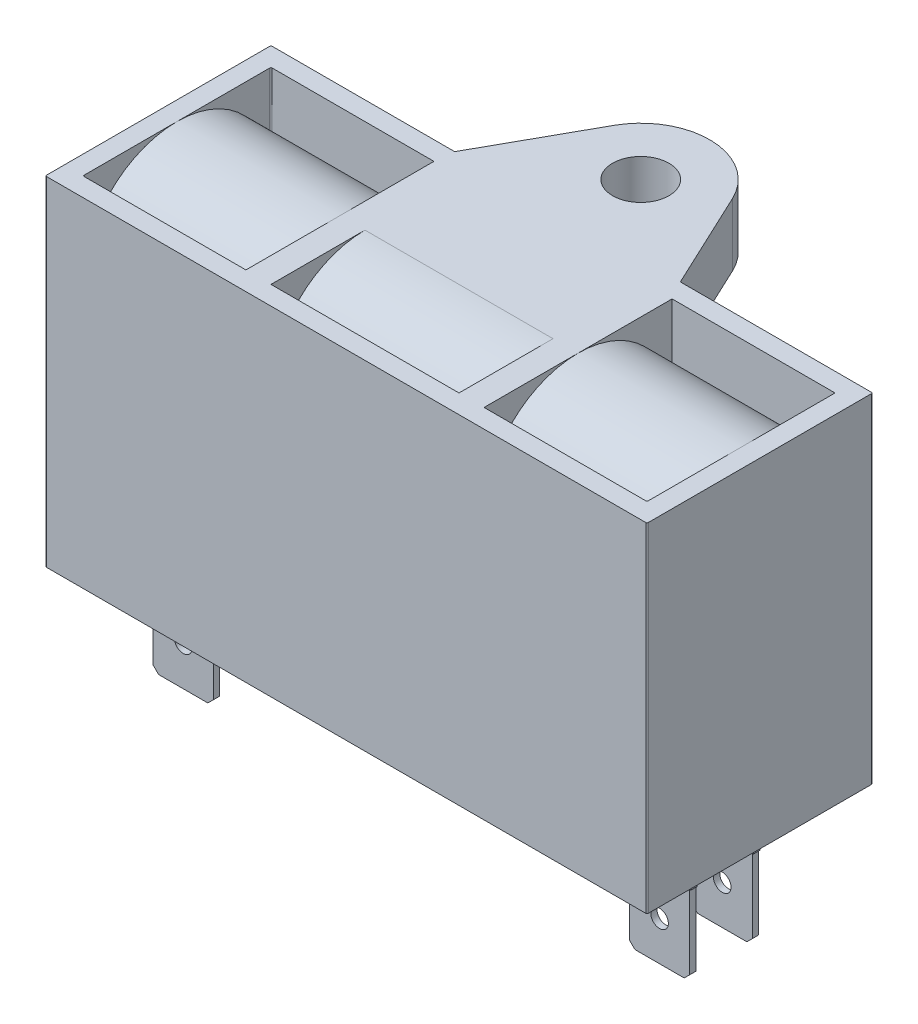
SolidWorks part; units mm, degrees
ref_plane "Front Plane" through (0, 0, 0) normal (0, 0, 1) x (1, 0, 0)
ref_plane "Top Plane" through (0, 0, 0) normal (0, 1, 0) x (1, 0, 0)
ref_plane "Right Plane" through (0, 0, 0) normal (1, 0, 0) x (0, 0, -1)
sketch "Sketch1" plane through (0, 0, 0) normal (0, 1, 0) x (1, 0, 0)
  line L1 (-24, 9) -> (24, 9)
  line L2 (-24, 9) -> (-24, -9)
  line L3 (-24, -9) -> (24, -9)
  line L4 (24, 9) -> (24, -9)
  line L5 (-24, 9) -> (24, -9) construction
  line L6 (-24, -9) -> (24, 9) construction
  point P0 (0, 0)
  dimension "D1" = 48
  dimension "D2" = 18
extrude "Boss-Extrude1" add sketch "Sketch1" along normal blind 27
sketch "Sketch7" plane through (0, 27, 0) normal (0, 1, 0) x (1, 0, 0)
  line L14 (22.5, -7.5) -> (22.5, 7.5)
  line L15 (22.5, 7.5) -> (-22.5, 7.5)
  line L16 (-22.5, 7.5) -> (-22.5, -7.5)
  line L17 (-22.5, -7.5) -> (22.5, -7.5)
  line L18 (22.5, -7.5) -> (22.5, 7.5)
  line L19 (22.5, 7.5) -> (-22.5, 7.5)
  line L20 (-22.5, 7.5) -> (-22.5, -7.5)
  line L21 (-22.5, -7.5) -> (22.5, -7.5)
  dimension "D1" = 1.5
extrude "Cut-Extrude8" cut sketch "Sketch7" against normal through all
sketch "Sketch9" plane through (22.5, 0, 0) normal (-1, 0, 0) x (0, 0, 1)
  line L0 (7.5, 27) -> (-7.5, 27) construction
  line L1 (-7.5, 0) -> (-7.5, 27) construction
  line L2 (7.5, 0) -> (7.5, 27) construction
  line L3 (-7.5, 0) -> (-7.5, 19.5)
  line L4 (7.5, 0) -> (7.5, 19.5)
  line L5 (7.5, 0) -> (-7.5, 0) construction
  line L6 (7.5, 0) -> (-7.5, 0)
  arc A0 (7.5, 19.5) -> (-7.5, 19.5) centre (0, 19.5) ccw
extrude "Boss-Extrude4" add sketch "Sketch9" along normal up to next separate body
sketch "Sketch10" plane through (0, 27, 0) normal (0, 1, 0) x (1, 0, 0)
  line L0 (24, 9) -> (-24, 9) construction
  line L1 (-7.5, 9) -> (-9.5, 9)
  line L2 (-7.5, 9) -> (-7.5, -9)
  line L3 (-7.5, -9) -> (-9.5, -9)
  line L4 (-9.5, 9) -> (-9.5, -9)
  line L5 (-24, -9) -> (24, -9) construction
  line L7 (-22.5, 7.5) -> (-22.5, -7.5) construction
  line L8 (22.5, -7.5) -> (22.5, 7.5) construction
  line L9 (7.5, 9) -> (9.5, 9)
  line L10 (7.5, 9) -> (7.5, -9)
  line L11 (7.5, -9) -> (9.5, -9)
  line L12 (9.5, 9) -> (9.5, -9)
  line M7 (22.5, -7.5) -> (-22.5, -7.5)
  line M9 (-22.5, 7.5) -> (22.5, 7.5)
  dimension "D1" = 13
  dimension "D2" = 2
  dimension "D3" = 2
  dimension "D4" = 13
extrude "Boss-Extrude5" add sketch "Sketch10" against normal up to next (27 mm away) contours L12 L10 M9 M7 | L4 L2 M9 M7 region at (-8.5, 27, 0) region at (8.5, 27, 0)
sketch "Sketch11" plane through (0, 27, 0) normal (0, 1, 0) x (1, 0, 0)
  line L0 (0, 9) -> (0, 14.5) construction
  line L1 (24, 9) -> (-24, 9) construction
  line L5 (-9.3433, 9) -> (8.6567, 9)
  line L10 (-9.3433, 9) -> (-4.8089, 17.1692)
  line L11 (8.6567, 9) -> (4.979, 16.8366)
  circle A0 centre (0, 14.5) radius 2.25
  arc A2 (4.979, 16.8366) -> (-4.8089, 17.1692) centre (0, 14.5) ccw
  point P9 (0, 9)
  line M22 (24, 9) -> (-24, 9)
  dimension "D2" = 4.5
  dimension "D1" = 5.5
  dimension "D3" = 18
extrude "Boss-Extrude7" add sketch "Sketch11" against normal blind 5 contours A0 M22 region at (-6.8916, 27, -12.9822)
fillet "Fillet1" radius 0.5 1 edges at (-0.3433, 22, -9)
sketch "Sketch12" plane through (0, 0, 0) normal (0, -1, 0) x (1, 0, 0)
  line L8 (22.5, -7.5) -> (22.5, 7.5)
  line L9 (22.5, 7.5) -> (-22.5, 7.5)
  line L10 (-22.5, 7.5) -> (-22.5, -7.5)
  line L11 (-22.5, -7.5) -> (22.5, -7.5)
  line L12 (22.5, -7.5) -> (22.5, 7.5)
  line L13 (22.5, 7.5) -> (-22.5, 7.5)
  line L14 (-22.5, 7.5) -> (-22.5, -7.5)
  line L15 (-22.5, -7.5) -> (22.5, -7.5)
  dimension "D1" = 1.5
extrude "Cut-Extrude9" cut sketch "Sketch12" against normal blind 0.5 contours L12 L13 L14 L15
ref_plane "Plane1" through (0, 0.5, 0) normal (0, -1, 0) x (-1, 0, 0)
sketch "Sketch15" plane through (0, 0, 0) normal (0, 0, 1) x (1, 0, 0)
  line L0 (-8.25, 0.5) -> (8.25, 0.5) construction
  line L1 (21.5, 0.5) -> (16.5, 0.5)
  line L2 (21.5, 0.5) -> (21.5, -2.6)
  line L4 (16.5, 0.5) -> (16.5, -2.6)
  line L5 (21.5, -2.6) -> (21.4, -2.6)
  line L7 (-24, 0) -> (24, 0) construction
  line L8 (21.4, -8.5) -> (21.4, -2.6)
  line L10 (16.6, -8.5) -> (16.6, -2.6)
  line L11 (21.4, -8.5) -> (16.6, -8.5) construction
  line L12 (21.4, -8.5) -> (20.964, -8.936)
  line L13 (17.036, -8.936) -> (16.6, -8.5)
  line L14 (16.6, -2.6) -> (16.5, -2.6)
  line L15 (24, 27) -> (24, 0) construction
  line L16 (20.964, -8.936) -> (17.036, -8.936)
  circle A0 centre (19, -5.8) radius 0.7
  point P10 (19, -8.5)
  dimension "D6" = 1.4
  dimension "D1" = 4.8
  dimension "D2" = 45
  dimension "D3" = 2.6
  dimension "D4" = 5
  dimension "D8" = 2.5
  dimension "D9" = 0.1
  dimension "D10" = 45
extrude "Boss-Extrude8" add sketch "Sketch15" along normal blind 0.5 from offset 2.5 separate body
extrude "Boss-Extrude9" add sketch "Sketch15<2>" along normal blind 0.5 from offset 2.5 offset against normal yes
sketch "Sketch15<2>" plane through (0, 0, 0) normal (0, 0, 1) x (1, 0, 0) same geometry as "Sketch15"
mirror "Mirror1" about plane through (0, 0, 0) normal (1, 0, 0) of "Boss-Extrude9", "Boss-Extrude8"
fillet "Fillet2" radius 0.1 8 edges at (-22.5, 23.25, -7.5) (-22.5, 23.25, 7.5) (22.5, 23.25, 7.5) (22.5, 23.25, -7.5) (24, 13.5, 9) (24, 13.5, -9) (-24, 13.5, 9) (-24, 13.5, -9)
sketch "Sketch16" plane through (0, 0, -7.5) normal (0, 0, 1) x (1, 0, 0)
  line L4 (-7.5, 27) -> (-7.5, 19.5)
  line L5 (-7.5, 19.5) -> (7.5, 19.5)
  line L6 (7.5, 19.5) -> (7.5, 27)
  line L7 (7.5, 27) -> (-7.5, 27)
  line L8 (-7.5, 27) -> (-7.5, 19.5)
  line L9 (-7.5, 19.5) -> (7.5, 19.5)
  line L10 (7.5, 19.5) -> (7.5, 27)
  line L11 (7.5, 27) -> (-7.5, 27)
  dimension "D1" = 0
extrude "Boss-Extrude10" add sketch "Sketch16" along normal up to next
fillet "Fillet3" radius 0.1 4 edges at (22.5, 0.25, 7.5) (22.5, 0.25, -7.5) (-22.5, 0.25, 7.5) (-22.5, 0.25, -7.5)
